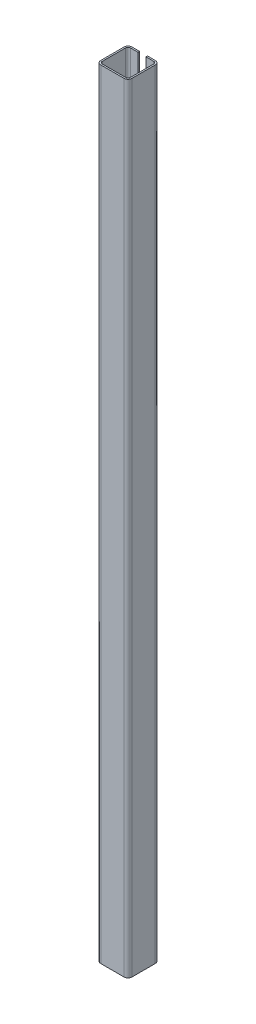
SolidWorks part; units mm, degrees
ref_plane "Спереди" through (0, 0, 0) normal (0, 0, 1) x (1, 0, 0)
ref_plane "Сверху" through (0, 0, 0) normal (0, 1, 0) x (1, 0, 0)
ref_plane "Справа" through (0, 0, 0) normal (1, 0, 0) x (0, 0, -1)
sketch "Эскиз1" plane through (0, 0, 0) normal (0, 1, 0) x (1, 0, 0)
  line L0 (-15, 0) -> (15, 0)
  line L1 (20, 5) -> (20, 35)
  line L2 (5, 40) -> (15, 40)
  line L3 (-20, 5) -> (-20, 35)
  line L4 (-15, 40) -> (-5, 40)
  arc A0 (-20, 35) -> (-15, 40) centre (-15, 35) cw
  arc A1 (20, 35) -> (15, 40) centre (15, 35) ccw
  arc A2 (15, 0) -> (20, 5) centre (15, 5) ccw
  arc A3 (-15, 0) -> (-20, 5) centre (-15, 5) cw
  point P6 (15.5601, 14.6248)
  dimension "D1" = 5
extrude "Вытянуть-Тонкостенный1" add sketch "Эскиз1" along normal blind 1000 thin thin type one direction wall 2
